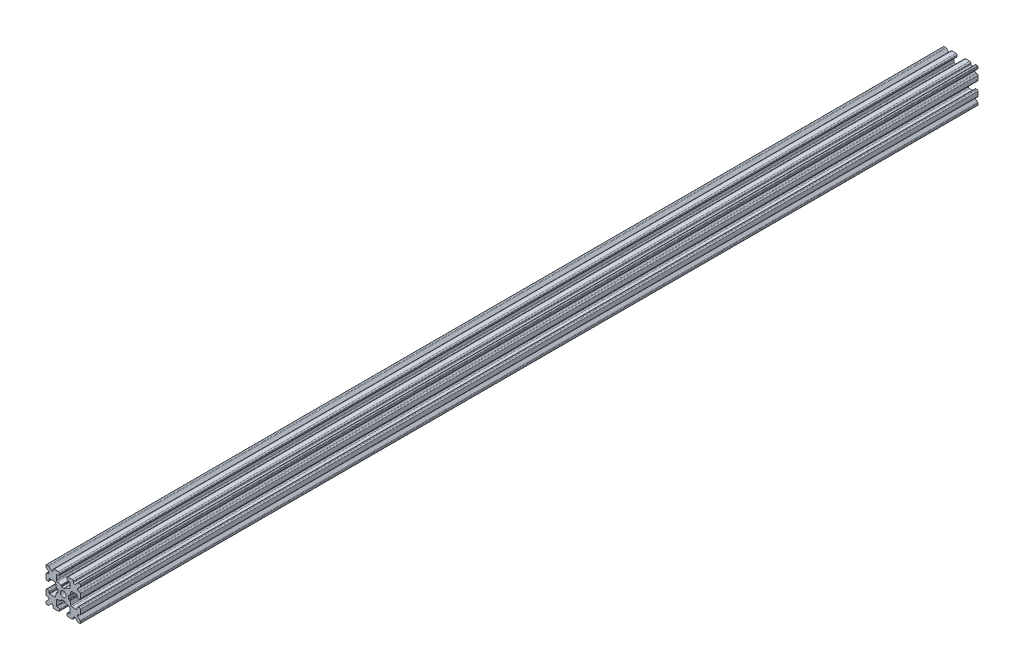
SolidWorks part; units mm, degrees
material "1060 Alloy"
ref_plane "Front Plane" through (0, 0, 0) normal (0, 0, 1) x (1, 0, 0)
ref_plane "Top Plane" through (0, 0, 0) normal (0, 1, 0) x (1, 0, 0)
ref_plane "Right Plane" through (0, 0, 0) normal (1, 0, 0) x (0, 0, -1)
sketch "Sketch1" plane through (0, 0, 0) normal (0, 0, 1) x (1, 0, 0)
  line L1 (-7.5, -7.5) -> (7.5, -7.5)
  line L2 (-7.5, -7.5) -> (-7.5, 7.5)
  line L3 (-7.5, 7.5) -> (7.5, 7.5)
  line L4 (7.5, -7.5) -> (7.5, 7.5)
  line L5 (-7.5, -7.5) -> (7.5, 7.5) construction
  line L6 (-7.5, 7.5) -> (7.5, -7.5) construction
  circle A0 centre (0, 0) radius 1.25
  point P0 (0, 0)
  dimension "D2" = 2.5
  dimension "D1" = 15
extrude "Boss-Extrude1" add sketch "Sketch1" along normal mid plane 392
fillet "Fillet1" radius 0.25 4 edges at (7.5, -7.5, 0) (-7.5, -7.5, 0) (7.5, 7.5, 0) (-7.5, 7.5, 0)
sketch "Sketch2" plane through (0, 0, 196) normal (0, 0, 1) x (1, 0, 0)
  line L0 (-7.5, 7.25) -> (-7.5, -7.25) construction
  line L1 (-7.5, 1.6) -> (-6.1, 1.6)
  line L2 (-7.5, 1.6) -> (-7.5, -1.6)
  line L3 (-7.5, -1.6) -> (-6.1, -1.6)
  line L4 (-6.1, 1.6) -> (-6.1, 2.9)
  line L5 (0, 0) -> (-12.1036, 0) construction
  line L6 (-6.1, -2.9) -> (-3.4, -2.9)
  line L7 (0, 0) -> (-7.25, 7.25) construction
  line L8 (-6.1, 2.9) -> (-3.4, 2.9)
  line L9 (-3.4, -2.9) -> (-3.4, 2.9)
  line L10 (55, 0) -> (-55, 0) construction
  line L11 (-6.1, -2.9) -> (-6.1, -1.6)
  line L12 (2.9, 6.1) -> (1.6, 6.1)
  line L13 (2.9, 3.4) -> (-2.9, 3.4)
  line L14 (-2.9, 6.1) -> (-2.9, 3.4)
  line L15 (2.9, 6.1) -> (2.9, 3.4)
  line L16 (-1.6, 6.1) -> (-2.9, 6.1)
  line L17 (1.6, 7.5) -> (1.6, 6.1)
  line L18 (-1.6, 7.5) -> (1.6, 7.5)
  line L19 (-1.6, 7.5) -> (-1.6, 6.1)
  line L20 (-1.6, -7.5) -> (-1.6, -6.1)
  line L21 (-1.6, -7.5) -> (1.6, -7.5)
  line L22 (1.6, -7.5) -> (1.6, -6.1)
  line L23 (-1.6, -6.1) -> (-2.9, -6.1)
  line L24 (2.9, -6.1) -> (2.9, -3.4)
  line L25 (-2.9, -6.1) -> (-2.9, -3.4)
  line L26 (2.9, -3.4) -> (-2.9, -3.4)
  line L27 (2.9, -6.1) -> (1.6, -6.1)
  line L28 (6.1, -2.9) -> (6.1, -1.6)
  line L29 (3.4, -2.9) -> (3.4, 2.9)
  line L30 (6.1, 2.9) -> (3.4, 2.9)
  line L31 (6.1, -2.9) -> (3.4, -2.9)
  line L32 (6.1, 1.6) -> (6.1, 2.9)
  line L33 (7.5, -1.6) -> (6.1, -1.6)
  line L34 (7.5, 1.6) -> (7.5, -1.6)
  line L35 (7.5, 1.6) -> (6.1, 1.6)
  dimension "D1" = 3.2
  dimension "D2" = 5.8
  dimension "D3" = 1.4
  dimension "D4" = 2.7
extrude "Cut-Extrude1" cut sketch "Sketch2" against normal through all
sketch "Sketch4" plane through (0, 0, 196) normal (0, 0, 1) x (1, 0, 0)
  line L0 (-3.4, 2.9) -> (-2.75, 0)
  line L1 (55, 0) -> (-55, 0) construction
  line L2 (-2.75, 0) -> (-3.4, -2.9)
  line L3 (-3.4, -2.9) -> (-3.4, 2.9) construction
  line L4 (-3.4, 2.9) -> (-3.4, -2.9)
  line L5 (-2.9, 3.4) -> (0, 2.75)
  line L6 (0, 2.75) -> (2.9, 3.4)
  line L7 (2.9, 3.4) -> (-2.9, 3.4)
  line L8 (3.4, 2.9) -> (2.75, 0)
  line L9 (2.75, 0) -> (3.4, -2.9)
  line L10 (3.4, -2.9) -> (3.4, 2.9)
  line L11 (-2.9, -3.4) -> (0, -2.75)
  line L12 (0, -2.75) -> (2.9, -3.4)
  line L13 (2.9, -3.4) -> (-2.9, -3.4)
  circle A2 centre (0, 0) radius 2.75
  circle A3 centre (0, 0) radius 2.75 construction
  dimension "D1" = 1.5
extrude "Cut-Extrude3" cut sketch "Sketch4" against normal through all
fillet "Fillet3" radius 0.5 16 edges at (-6.1, -1.6, 0) (-7.5, -1.6, 0) (-6.1, 1.6, 0) (-7.5, 1.6, 0) (-1.6, -7.5, 0) (-1.6, -6.1, 0) (1.6, -7.5, 0) (1.6, -6.1, 0) (6.1, -1.6, 0) (7.5, -1.6, 0) (7.5, 1.6, 0) (6.1, 1.6, 0) (1.6, 7.5, 0) (1.6, 6.1, 0) (-1.6, 7.5, 0) (-1.6, 6.1, 0)
fillet "Fillet4" radius 0.5 8 edges at (-3.4, 2.9, 0) (-3.4, -2.9, 0) (2.9, -3.4, 0) (-2.9, -3.4, 0) (3.4, -2.9, 0) (3.4, 2.9, 0) (-2.9, 3.4, 0) (2.9, 3.4, 0)
fillet "Fillet5" radius 3 4 edges at (0, -2.75, 0) (2.75, 0, 0) (-2.75, 0, 0) (0, 2.75, 0)
fillet "Fillet6" radius 0.2 8 edges at (-2.9, -6.1, 0) (2.9, -6.1, 0) (6.1, -2.9, 0) (6.1, 2.9, 0) (2.9, 6.1, 0) (-2.9, 6.1, 0) (-6.1, -2.9, 0) (-6.1, 2.9, 0)
sketch "Sketch5" plane through (0, 0, 196) normal (0, 0, 1) x (1, 0, 0)
  line L0 (0, 0) -> (-7.25, 7.25) construction
  line L1 (-7.5, 6.4393) -> (-5.4607, 4.4)
  line L2 (-6.4393, 7.5) -> (-4.4, 5.4607)
  line L3 (-7.5, 4.4) -> (-5.4607, 4.4)
  line L4 (-3.8003, 2.9) -> (-5.9, 2.9) construction
  line L5 (0, 0) -> (-12.1819, 0) construction
  line L6 (-4.4, 7.5) -> (-4.4, 5.4607)
  line L7 (-2.9, 5.9) -> (-2.9, 3.8003) construction
  line L8 (-7.5, 6.4393) -> (-7.5, 4.4)
  line L9 (-7.5, 7.25) -> (-7.5, 2.1) construction
  line L10 (2.1, -7.5) -> (7.25, -7.5) construction
  line L11 (7.5, -7.25) -> (7.5, -2.1) construction
  line L12 (7.25, 7.5) -> (2.1, 7.5) construction
  line L13 (-2.1, 7.5) -> (-7.25, 7.5) construction
  line L14 (-4.4, 7.5) -> (-6.4393, 7.5)
  line L16 (55, 0) -> (-55, 0) construction
  line L17 (0, 0) -> (0, 10.993) construction
  line L18 (0, -54.6431) -> (0, 54.6431) construction
  line L20 (4.4, 7.5) -> (6.4393, 7.5)
  line L22 (7.5, 6.4393) -> (7.5, 4.4)
  line L23 (4.4, 7.5) -> (4.4, 5.4607)
  line L24 (7.5, 4.4) -> (5.4607, 4.4)
  line L25 (6.4393, 7.5) -> (4.4, 5.4607)
  line L26 (7.5, 6.4393) -> (5.4607, 4.4)
  line L27 (7.5, -6.4393) -> (5.4607, -4.4)
  line L28 (6.4393, -7.5) -> (4.4, -5.4607)
  line L29 (7.5, -4.4) -> (5.4607, -4.4)
  line L30 (4.4, -7.5) -> (4.4, -5.4607)
  line L31 (7.5, -6.4393) -> (7.5, -4.4)
  line L33 (4.4, -7.5) -> (6.4393, -7.5)
  line L36 (-4.4, -7.5) -> (-6.4393, -7.5)
  line L38 (-7.5, -6.4393) -> (-7.5, -4.4)
  line L39 (-4.4, -7.5) -> (-4.4, -5.4607)
  line L40 (-7.5, -4.4) -> (-5.4607, -4.4)
  line L41 (-6.4393, -7.5) -> (-4.4, -5.4607)
  line L42 (-7.5, -6.4393) -> (-5.4607, -4.4)
  dimension "D1" = 1.5
  dimension "D2" = 1.5
  dimension "D3" = 1.5
extrude "Cut-Extrude4" cut sketch "Sketch5" against normal through all
fillet "Fillet8" radius 0.5 24 edges at (-5.4607, 4.4, 0) (-7.5, 4.4, 0) (-5.4607, -4.4, 0) (-7.5, -4.4, 0) (-4.4, -7.5, 0) (-4.4, -5.4607, 0) (4.4, -7.5, 0) (4.4, -5.4607, 0) (5.4607, -4.4, 0) (7.5, -4.4, 0) (7.5, 4.4, 0) (5.4607, 4.4, 0) (4.4, 5.4607, 0) (4.4, 7.5, 0) (-4.4, 5.4607, 0) (-4.4, 7.5, 0) (-6.4393, 7.5, 0) (-7.5, 6.4393, 0) (6.4393, 7.5, 0) (7.5, 6.4393, 0) (6.4393, -7.5, 0) (7.5, -6.4393, 0) (-6.4393, -7.5, 0) (-7.5, -6.4393, 0)
sketch "Sketch6" plane through (0, 0, 196) normal (0, 0, 1) x (1, 0, 0)
  line L0 (0, 0) -> (0, 11.013) construction
  line L1 (0.6561, 2.8971) -> (2.1235, 2.8971) construction
  line L2 (0, -54.6431) -> (0, 54.6431) construction
  line L3 (0, 0) -> (7.25, 7.25) construction
  line L4 (7.5, 0.8255) -> (7.5, -0.8255)
  line L5 (2.3471, 0.8255) -> (7.5, 0.8255)
  line L6 (0, 0) -> (12.4016, 0) construction
  line L7 (0.8255, -7.5) -> (-0.8255, -7.5)
  line L8 (2.3471, -0.8255) -> (2.3471, 0.8255)
  line L9 (0.8255, -2.3471) -> (0.8255, -7.5)
  line L10 (7.5, -0.8255) -> (2.3471, -0.8255)
  line L11 (-7.5, -0.8255) -> (-2.3471, -0.8255)
  line L12 (-2.3471, -0.8255) -> (-2.3471, 0.8255)
  line L13 (-0.8255, -2.3471) -> (0.8255, -2.3471)
  line L14 (-0.8255, 7.5) -> (-0.8255, 2.3471)
  line L15 (-0.8255, 2.3471) -> (0.8255, 2.3471)
  line L16 (-0.8255, -7.5) -> (-0.8255, -2.3471)
  line L17 (0.8255, 2.3471) -> (0.8255, 7.5)
  line L18 (0.8255, 7.5) -> (-0.8255, 7.5)
  line L19 (3.9, 7.5) -> (2.1, 7.5) construction
  line L20 (-2.3471, 0.8255) -> (-7.5, 0.8255)
  line L21 (-7.5, 0.8255) -> (-7.5, -0.8255)
  point P5 (0, -2.5973)
  point P7 (0, 2.5973)
  dimension "D3" = 0.55
  dimension "D1" = 1.651
extrude "Cut-Extrude5" cut sketch "Sketch6" against normal through all
fillet "Fillet10" radius 0.2 16 edges at (-2.935, 0.8255, 0) (-2.935, -0.8255, 0) (2.935, -0.8255, 0) (2.935, 0.8255, 0) (0.8255, 2.935, 0) (-0.8255, 2.935, 0) (-2.3471, 0.8255, 0) (-2.3471, -0.8255, 0) (0.8255, 2.3471, 0) (-0.8255, 2.3471, 0) (2.3471, 0.8255, 0) (2.3471, -0.8255, 0) (0.8255, -2.935, 0) (0.8255, -2.3471, 0) (-0.8255, -2.3471, 0) (-0.8255, -2.935, 0)
